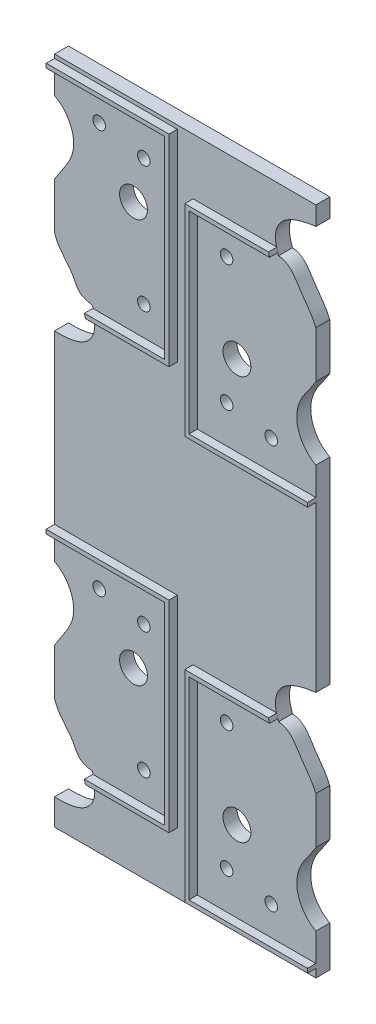
SolidWorks part; units mm, degrees
ref_plane "Front Plane" through (0, 0, 0) normal (0, 0, 1) x (1, 0, 0)
ref_plane "Top Plane" through (0, 0, 0) normal (0, 1, 0) x (1, 0, 0)
ref_plane "Right Plane" through (0, 0, 0) normal (1, 0, 0) x (0, 0, -1)
sketch "Sketch1" plane through (0, 0, 0) normal (0, 0, 1) x (1, 0, 0)
  line L0 (-19.7692, 94.7302) -> (-48.0392, 94.7302) construction
  line L1 (-46.8389, 110) -> (46.8389, 110)
  line L2 (-46.8389, 110) -> (-46.8389, -70)
  line L3 (-46.8389, -70) -> (46.8389, -70)
  line L4 (46.8389, 110) -> (46.8389, -70)
  line L5 (-46.8389, 27.4128) -> (-46.8389, 58.1094)
  line L6 (-46.8389, 100.4217) -> (-46.8597, 74.4838)
  line L7 (46.8389, 13.6344) -> (46.8389, -17.7446)
  line L8 (46.8389, 106.6344) -> (46.8389, 75.2554)
  line L9 (46.8389, 32.5783) -> (46.8597, 58.5162)
  line L10 (46.8389, -60.4217) -> (46.8597, -34.4838)
  line L11 (-46.8389, -65.5872) -> (-46.8389, -34.8906)
  line L12 (-46.8389, 7.4217) -> (-46.8597, -18.5162)
  line L14 (0, -70) -> (-46.8389, -70)
  line L15 (-46.8389, -34.8906) -> (-46.8389, -70)
  line L16 (33.4436, 90.8587) -> (0, 110)
  line L17 (-46.8389, -65.5872) -> (-46.8389, -70)
  line L18 (0, -70) -> (-46.8389, -70)
  arc A0 (-42.3622, 81.2908) -> (-46.8389, 100.4217) centre (-53.2184, 88.8396) ccw construction
  arc A1 (-42.3622, 81.2908) -> (-46.8597, 74.4838) centre (98.8539, -16.903) ccw construction
  arc A2 (-44.9811, 54.2562) -> (-41.0297, 48.7592) centre (4.5296, 85.6771) ccw construction
  arc A3 (-38.5976, 44.9453) -> (-41.0297, 48.7592) centre (-56.5685, 36.1677) ccw construction
  arc A4 (-40.9236, 48.3818) -> (-37.2194, 45.4511) centre (-33.0423, 54.5369) ccw construction
  arc A5 (-38.5976, 44.9453) -> (-36.9529, 43.1656) centre (-34.8111, 46.7947) ccw construction
  arc A6 (-36.9529, 43.1656) -> (-29.4469, 41.75) centre (-29.4469, 62.3575) ccw construction
  circle A7 centre (-14.8389, 51.75) radius 2.25
  arc A8 (42.3622, 51.7092) -> (46.8389, 32.5783) centre (53.2184, 44.1604) ccw construction
  arc A9 (42.3622, 51.7092) -> (46.8597, 58.5162) centre (-98.8539, 149.903) ccw construction
  arc A10 (36.9529, 89.8344) -> (29.4469, 91.25) centre (29.4469, 70.6425) ccw construction
  circle A11 centre (-14.8389, 97) radius 2.25
  circle A12 centre (-30.8389, 100) radius 2.25
  circle A13 centre (14.8389, 81.25) radius 2.25
  circle A14 centre (14.8389, 36) radius 2.25
  circle A15 centre (30.8389, 33) radius 2.25
  circle A16 centre (-14.8389, -41.25) radius 2.25
  circle A17 centre (-14.8389, 4) radius 2.25
  circle A18 centre (-30.8389, 7) radius 2.25
  circle A19 centre (14.8389, -11.75) radius 2.25
  circle A20 centre (14.8389, -57) radius 2.25
  circle A21 centre (30.8389, -60) radius 2.25
  spline S0 degree 3 poles (-46.8389, 100.4217) (-42.2264, 98.1412) (-36.7036, 86.8939) (-44.5501, 78.531) (-46.8597, 74.4838) knots 0 0 0 0 0.513387 1 1 1 1
  spline S1 degree 3 poles (-46.8389, 58.1094) (-45.7586, 53.6552) (-40.8859, 50.4065) (-38.2385, 43.1366) (-34.7821, 42.4316) (-33.2661, 42.107) knots 0 0 0 0 0.587735 0.769686 1 1 1 1
  spline S2 degree 2 poles (-33.2661, 42.107) (-28.8924, 26.7095) (-46.8389, 27.4128) knots 0 0 0 1 1 1
  spline S3 degree 3 poles (46.8389, 32.5783) (42.9828, 34.6042) (38.9062, 41.1287) (41.1418, 51.3815) (45.2094, 55.5599) (46.8597, 58.5162) knots 0 0 0 0 0.434931 0.661678 1 1 1 1
  spline S4 degree 3 poles (46.8389, 75.2554) (45.396, 78.7223) (40.759, 83.9953) (37.5733, 90.552) (33.4436, 90.8587) knots 0 0 0 0 0.525455 1 1 1 1
  spline S5 degree 2 poles (-33.2661, -50.893) (-28.8924, -66.2905) (-46.8389, -65.5872) knots 0 0 0 1 1 1
  spline S7 degree 3 poles (-46.8389, -34.8906) (-45.7586, -39.3448) (-40.8859, -42.5935) (-38.2385, -49.8634) (-34.7821, -50.5684) (-33.2661, -50.893) knots 0 0 0 0 0.587735 0.769686 1 1 1 1
  spline S8 degree 3 poles (-46.8389, 7.4217) (-42.2264, 5.1412) (-36.7036, -6.1061) (-44.5501, -14.469) (-46.8597, -18.5162) knots 0 0 0 0 0.513387 1 1 1 1
  spline S9 degree 2 poles (33.4436, -2.1413) (28.4165, 11.5595) (46.8389, 13.6344) knots 0 0 0 1 1 1
  spline S10 degree 3 poles (46.8389, -17.7446) (45.396, -14.2777) (40.759, -9.0047) (37.5733, -2.448) (33.4436, -2.1413) knots 0 0 0 0 0.525455 1 1 1 1
  spline S11 degree 3 poles (46.8389, -60.4217) (42.9828, -58.3958) (38.9062, -51.8713) (41.1418, -41.6185) (45.2094, -37.4401) (46.8597, -34.4838) knots 0 0 0 0 0.434931 0.661678 1 1 1 1
  dimension "D1" = 4.5
  dimension "D2" = 4.5
  dimension "D3" = 4.5
  dimension "D4" = 4.5
  dimension "D6" = 44.75
  dimension "D5" = 2
extrude "Boss-Extrude1" add sketch "Sketch1" along normal blind 5 contours L4 S11 S10 S9 S3 S4 L1 L2 S0 S1 S2 S8 S7 L3 region at (-0.6675, 17.7972, 0)
sketch "Sketch7" plane through (0, 0, 5) normal (0, 0, 1) x (1, 0, 0)
  circle A0 centre (-41.8389, 23.5) radius 2
  circle A1 centre (-41.8389, 67) radius 2
  circle A2 centre (40.8611, 67) radius 2
  circle A3 centre (40.8611, 23.5) radius 2
  dimension "D1" = 4
  dimension "D2" = 4
  dimension "D3" = 4
  dimension "D4" = 4
extrude "Cut-Extrude1" cut sketch "Sketch7" against normal blind 10
sketch "Sketch8" plane through (0, 0, 0) normal (0, 0, -1) x (-1, 0, 0)
  circle A0 centre (-18.5389, -41.6) radius 5
  circle A1 centre (-18.5389, 51.4) radius 5
  circle A2 centre (18.5389, 81.6) radius 5
  circle A3 centre (18.5389, -11.4) radius 5
  dimension "D1" = 10
extrude "Cut-Extrude2" cut sketch "Sketch8" against normal blind 10
sketch "Sketch10" plane through (0, 0, 5) normal (0, 0, 1) x (1, 0, 0)
  line L0 (46.8389, 32.5783) -> (46.8389, 13.6344) construction
  line L1 (-46.8389, 110) -> (46.8389, 110)
  line L2 (-46.8389, 110) -> (-46.8389, 20.3513)
  line L3 (-46.8389, 20.3513) -> (46.8389, 20.3513)
  line L4 (46.8389, 110) -> (46.8389, 20.3513)
extrude "Cut-Extrude4" cut sketch "Sketch10" against normal blind 10
pattern_linear "LPattern1" count 2 spacing 144.65 along (0, -1, 0) of bodies 108
sketch "Sketch13" plane through (0, 0, 5) normal (0, 0, 1) x (1, 0, 0)
  line L1 (-46.8389, -70) -> (46.8389, -70)
  line L2 (-46.8389, -70) -> (-46.8389, -124.2987)
  line L3 (-46.8389, -124.2987) -> (46.8389, -124.2987)
  line L4 (46.8389, -70) -> (46.8389, -124.2987)
extrude "Boss-Extrude2" add sketch "Sketch13" against normal up to surface (5 mm away) up to face at (13.5389, -41.6, 0)
sketch "Sketch18" plane through (0, 0, 5) normal (0, 0, 1) x (1, 0, 0)
  line L1 (-46.8389, -214.65) -> (46.8389, -214.65)
  line L2 (-46.8389, -214.65) -> (-46.8389, -219.65)
  line L3 (-46.8389, -219.65) -> (46.8389, -219.65)
  line L4 (46.8389, -214.65) -> (46.8389, -219.65)
  point P5 (46.7704, -214.65)
  dimension "D1" = 5
extrude "Boss-Extrude5" add sketch "Sketch18" against normal up to surface (5 mm away) up to face at (13.5389, -41.6, 0)
sketch "Sketch17" plane through (0, 0, 5) normal (0, 0, 1) x (1, 0, 0)
  line L0 (33.1375, -1.25) -> (4.3389, -1.25)
  line L1 (4.3389, -1.25) -> (4.3389, -70.5)
  line L2 (4.3389, -70.5) -> (46.8389, -70.5)
  line L3 (46.8389, -60.4217) -> (46.8389, -131.0156) construction
  line L4 (32.842, 0.25) -> (2.8389, 0.25)
  line L5 (2.8389, 0.25) -> (2.8389, -72)
  line L6 (2.8389, -72) -> (46.8389, -72)
  line L7 (-33.0368, -51.75) -> (-4.3389, -51.75)
  line L8 (-4.3389, -51.75) -> (-4.3389, 17.5)
  line L9 (-4.3389, 17.5) -> (-46.8389, 17.5)
  line L10 (-46.8389, 20.3513) -> (-46.8389, 7.4217) construction
  line L11 (-32.8146, -53.25) -> (-2.8389, -53.25)
  line L12 (-2.8389, -53.25) -> (-2.8389, 19)
  line L13 (-2.8389, 19) -> (-46.8389, 19)
  line L14 (-33.0368, -196.4) -> (-4.3389, -196.4)
  line L15 (-4.3389, -196.4) -> (-4.3389, -127.15)
  line L16 (-4.3389, -127.15) -> (-46.8389, -127.15)
  line L17 (-46.8389, -65.5872) -> (-46.8389, -137.2283) construction
  line L18 (-32.8146, -197.9) -> (-2.8389, -197.9)
  line L19 (-2.8389, -197.9) -> (-2.8389, -125.65)
  line L20 (-2.8389, -125.65) -> (-46.8389, -125.65)
  line L21 (33.1375, -145.9) -> (4.3389, -145.9)
  line L22 (4.3389, -145.9) -> (4.3389, -215.15)
  line L23 (4.3389, -215.15) -> (46.8389, -215.15)
  line L24 (46.8389, -205.0717) -> (46.8389, -219.65) construction
  line L25 (32.842, -144.4) -> (2.8389, -144.4)
  line L26 (2.8389, -144.4) -> (2.8389, -216.65)
  line L27 (2.8389, -216.65) -> (46.8389, -216.65)
  line L28 (-46.8389, -125.65) -> (-46.8389, -127.15)
  line L30 (46.8389, -215.15) -> (46.8389, -216.65)
  line L33 (-46.8389, 19) -> (-46.8389, 17.5)
  line L35 (46.8389, -70.5) -> (46.8389, -72)
  line L36 (-33.0368, -51.75) -> (-33.107, -51.75)
  line L37 (-33.107, -51.75) -> (-32.8146, -53.25)
  line L38 (32.842, 0.25) -> (33.2251, -1.25)
  line L39 (-33.0368, -53.25) -> (-2.8389, -53.25) construction
  line L40 (33.2251, -1.25) -> (33.1375, -1.25)
  line L41 (-33.0368, -196.4) -> (-33.107, -196.4)
  line L42 (33.1375, 0.25) -> (2.8389, 0.25) construction
  line L43 (-33.107, -196.4) -> (-32.8146, -197.9)
  line L44 (32.842, -144.4) -> (33.2251, -145.9)
  line L45 (-33.0368, -197.9) -> (-2.8389, -197.9) construction
  line L46 (33.2251, -145.9) -> (33.1375, -145.9)
  line L48 (33.1375, -144.4) -> (2.8389, -144.4) construction
  circle A0 centre (14.8389, -11.75) radius 2.25 construction
  circle A1 centre (14.8389, -57) radius 2.25 construction
  circle A2 centre (-14.8389, 4) radius 2.25 construction
  circle A3 centre (-14.8389, -41.25) radius 2.25 construction
  circle A4 centre (-14.8389, -185.9) radius 2.25 construction
  circle A5 centre (-14.8389, -140.65) radius 2.25 construction
  circle A6 centre (14.8389, -201.65) radius 2.25 construction
  circle A7 centre (14.8389, -156.4) radius 2.25 construction
  parabola Q0 (33.4436, -2.1413) -> (46.8389, 13.6344) focus (36.6663, 5.3308) apex (33.2144, 7.0422) construction
  parabola Q1 (-33.2661, -50.893) -> (-46.8389, -65.5872) focus (-36.8258, -59.4952) apex (-33.9207, -61.5908) construction
  parabola Q2 (-33.2661, -195.543) -> (-46.8389, -210.2372) focus (-36.8258, -204.1452) apex (-33.9207, -206.2408) construction
  parabola Q3 (33.4436, -146.7913) -> (46.8389, -131.0156) focus (36.6663, -139.3192) apex (33.2144, -137.6078) construction
  dimension "D2" = 10.5
  dimension "D3" = 13.5
  dimension "D6" = 13.5
  dimension "D7" = 10.5
  dimension "D9" = 10.5
  dimension "D10" = 10.5
  dimension "D11" = 13.5
  dimension "D13" = 13.5
  dimension "D14" = 10.5
  dimension "D15" = 10.5
  dimension "D1" = 10.5
  dimension "D5" = 10.5
  dimension "D12" = 1.5
  dimension "D4" = 1.5
  dimension "D8" = 1.5
  dimension "D16" = 1.5
extrude "Boss-Extrude7" add sketch "Sketch17" along normal blind 3
